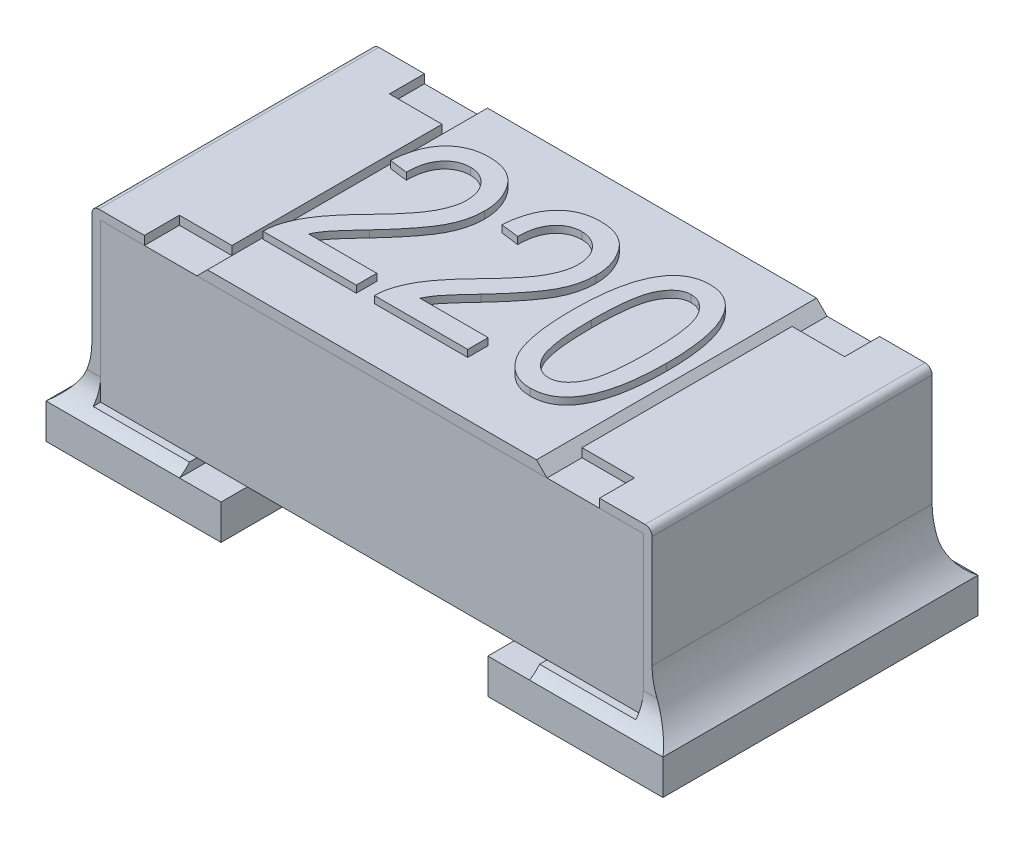
SolidWorks part; units mm, degrees
material "Ceramic Porcelain"
ref_plane "Front Plane" through (0, 0, 0) normal (0, 0, 1) x (1, 0, 0)
ref_plane "Top Plane" through (0, 0, 0) normal (0, 1, 0) x (1, 0, 0)
ref_plane "Right Plane" through (0, 0, 0) normal (1, 0, 0) x (0, 0, -1)
sketch "Sketch1" plane through (0, 0, 0) normal (1, 0, 0) x (0, 0, -1)
  line L0 (0, 55) -> (0, -55) construction
  line L1 (-0.4, 0.575) -> (0.4, 0.575)
  line L2 (-0.4, 0.575) -> (-0.4, 0.125)
  line L3 (-0.4, 0.125) -> (0.4, 0.125)
  line L4 (0.4, 0.575) -> (0.4, 0.125)
  line L5 (55, 0) -> (-55, 0) construction
  dimension "D1" = 0.8
  dimension "D2" = 0.4
  dimension "D3" = 0.45
  dimension "D4" = 0.125
extrude "Boss-Extrude1" add sketch "Sketch1" along normal mid plane 1.55
sketch "Sketch2" plane through (0, 0, 0) normal (0, 0, 1) x (1, 0, 0)
  line L0 (-0.5, 0.6) -> (-0.78, 0.6)
  line L1 (-0.8, 0.58) -> (-0.8, 0.1)
  line L2 (-0.8, 0.1) -> (-0.5, 0.1)
  line L3 (-0.5, 0.1) -> (-0.5, 0.125)
  line L4 (0.775, 0.125) -> (-0.775, 0.125) construction
  line L5 (-0.5, 0.125) -> (-0.775, 0.125)
  line L6 (-0.775, 0.125) -> (-0.775, 0.575)
  line L7 (-0.775, 0.575) -> (-0.5, 0.575)
  line L8 (0.775, 0.575) -> (-0.775, 0.575) construction
  line L9 (-0.5, 0.575) -> (-0.5, 0.6)
  line L11 (0.5, 0.575) -> (0.5, 0.6)
  line L12 (0.5, 0.6) -> (0.78, 0.6)
  line L13 (0.8, 0.58) -> (0.8, 0.1)
  line L14 (0.8, 0.1) -> (0.5, 0.1)
  line L15 (0.5, 0.1) -> (0.5, 0.125)
  line L16 (0.5, 0.125) -> (0.775, 0.125)
  line L17 (0.775, 0.125) -> (0.775, 0.575)
  line L18 (0.775, 0.575) -> (0.5, 0.575)
  arc A0 (0.78, 0.6) -> (0.8, 0.58) centre (0.78, 0.58) cw
  arc A1 (-0.78, 0.6) -> (-0.8, 0.58) centre (-0.78, 0.58) ccw
  point P28 (-0.8, 0.6)
  dimension "D6" = 0.02
  dimension "D1" = 0.025
  dimension "D2" = 0.025
  dimension "D3" = 0.025
  dimension "D4" = 0.3
  dimension "D5" = 0.3
extrude "Boss-Extrude2" add sketch "Sketch2" along normal mid plane 0.8 separate body
sketch "Sketch3" plane through (0, 0.6, 0) normal (0, 1, 0) x (1, 0, 0)
  line L0 (0.5, -0.4) -> (0.5, 0.4) construction
  line L1 (-0.5, 0.4) -> (-0.65, 0.4)
  line L2 (-0.5, 0.4) -> (-0.5, 0.3)
  line L3 (-0.5, 0.3) -> (-0.65, 0.3)
  line L4 (-0.65, 0.4) -> (-0.65, 0.3)
  line L5 (-0.5, -0.4) -> (-0.65, -0.4)
  line L6 (-0.5, -0.4) -> (-0.5, -0.3)
  line L7 (-0.5, -0.3) -> (-0.65, -0.3)
  line L8 (-0.65, -0.4) -> (-0.65, -0.3)
  line L9 (0.5, -0.4) -> (0.65, -0.4)
  line L10 (0.5, -0.4) -> (0.5, -0.3)
  line L11 (0.5, -0.3) -> (0.65, -0.3)
  line L12 (0.65, -0.4) -> (0.65, -0.3)
  line L13 (0.775, -0.4) -> (-0.775, -0.4) construction
  line L15 (0.5, 0.4) -> (0.65, 0.4)
  line L16 (0.5, 0.4) -> (0.5, 0.3)
  line L17 (0.5, 0.3) -> (0.65, 0.3)
  line L18 (0.65, 0.4) -> (0.65, 0.3)
  dimension "D1" = 0.15
  dimension "D2" = 0.1
extrude "Cut-Extrude1" cut sketch "Sketch3" against normal blind 0.025
sketch "Sketch4" plane through (0, 0, 0) normal (0, 0, 1) x (1, 0, 0)
  line L0 (-0.5, 0.575) -> (0.5, 0.575)
  line L1 (0.5, 0.575) -> (0.47, 0.605)
  line L2 (0.47, 0.605) -> (-0.47, 0.605)
  line L3 (-0.47, 0.605) -> (-0.5, 0.575)
  dimension "D1" = 45
  dimension "D2" = 45
  dimension "D3" = 0.03
extrude "Boss-Extrude3" add sketch "Sketch4" along normal mid plane 0.8 separate body
sketch "Sketch7" plane through (0, 0, 0) normal (0, 1, 0) x (1, 0, 0)
  line L0 (0, -0.2777) -> (0, 0.2777) construction
  line L1 (-0.381, -0.45) -> (-0.881, -0.45)
  line L2 (-0.381, -0.45) -> (-0.381, 0.45)
  line L3 (-0.381, 0.45) -> (-0.881, 0.45)
  line L4 (-0.881, -0.45) -> (-0.881, 0.45)
  line L5 (0.381, -0.45) -> (0.881, -0.45)
  line L6 (0.381, -0.45) -> (0.381, 0.45)
  line L7 (0.381, 0.45) -> (0.881, 0.45)
  line L8 (0.881, -0.45) -> (0.881, 0.45)
  line L9 (-0.2777, 0) -> (0.2777, 0) construction
  dimension "D1" = 0.5
  dimension "D2" = 0.381
  dimension "D3" = 0.381
  dimension "D4" = 0.9
  dimension "D5" = 0.45
extrude "Boss-Extrude5" add sketch "Sketch7" along normal blind 0.1
fillet "Fillet3" radius 0.2 1 edges at (-0.8, 0.1, 0)
fillet "Fillet4" radius 0.2 1 edges at (0.8, 0.1, 0)
fillet "Fillet5" radius 0.1 2 edges at (0.6905, 0.1, -0.4) (0.6905, 0.1, 0.4)
fillet "Fillet6" radius 0.1 2 edges at (-0.6905, 0.1, 0.4) (-0.6905, 0.1, -0.4)
sketch "Esquisse2" plane through (0, 0.605, 0) normal (0, 1, 0) x (1, 0, 0)
  text T0 "220" font "Arial Narrow" height 0.5
extrude "Boss.-Extru.1" add sketch "Esquisse2" along normal blind 0.02
